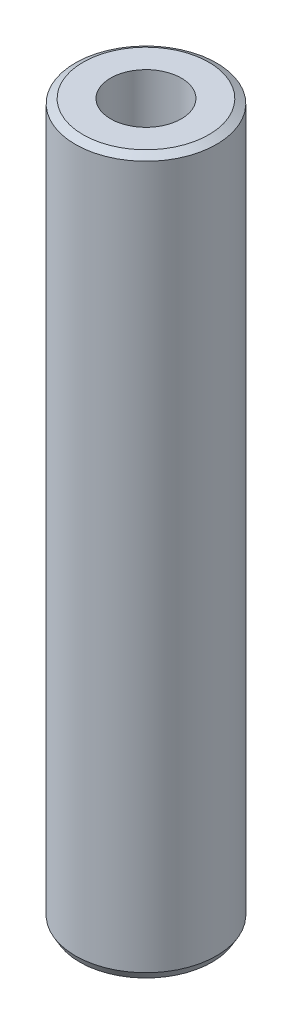
SolidWorks part; units mm, degrees
ref_plane "Front Plane" through (0, 0, 0) normal (0, 0, 1) x (1, 0, 0)
ref_plane "Top Plane" through (0, 0, 0) normal (0, 1, 0) x (1, 0, 0)
ref_plane "Right Plane" through (0, 0, 0) normal (1, 0, 0) x (0, 0, -1)
sketch "Sketch1" plane through (0, 0, 0) normal (0, 1, 0) x (1, 0, 0)
  circle A0 centre (0, 0) radius 55
  dimension "SHAFT_OD" = 110
extrude "Boss-Extrude1" add sketch "Sketch1" along normal blind 556.9119
sketch "Sketch2" plane through (0, 0, 0) normal (0, 1, 0) x (1, 0, 0)
  circle A0 centre (0, 0) radius 27.5492
  dimension "BORE_D" = 55.0985
extrude "Cut-Extrude1" cut sketch "Sketch2" along normal through all
chamfer "Chamfer1" distance 3.49 angle 60 2 edges at (0, 556.9119, 55) (0, 0, 55) first distance on face at (0, 556.9119, 55) first distance on face at (0, 0, 27.5492)
